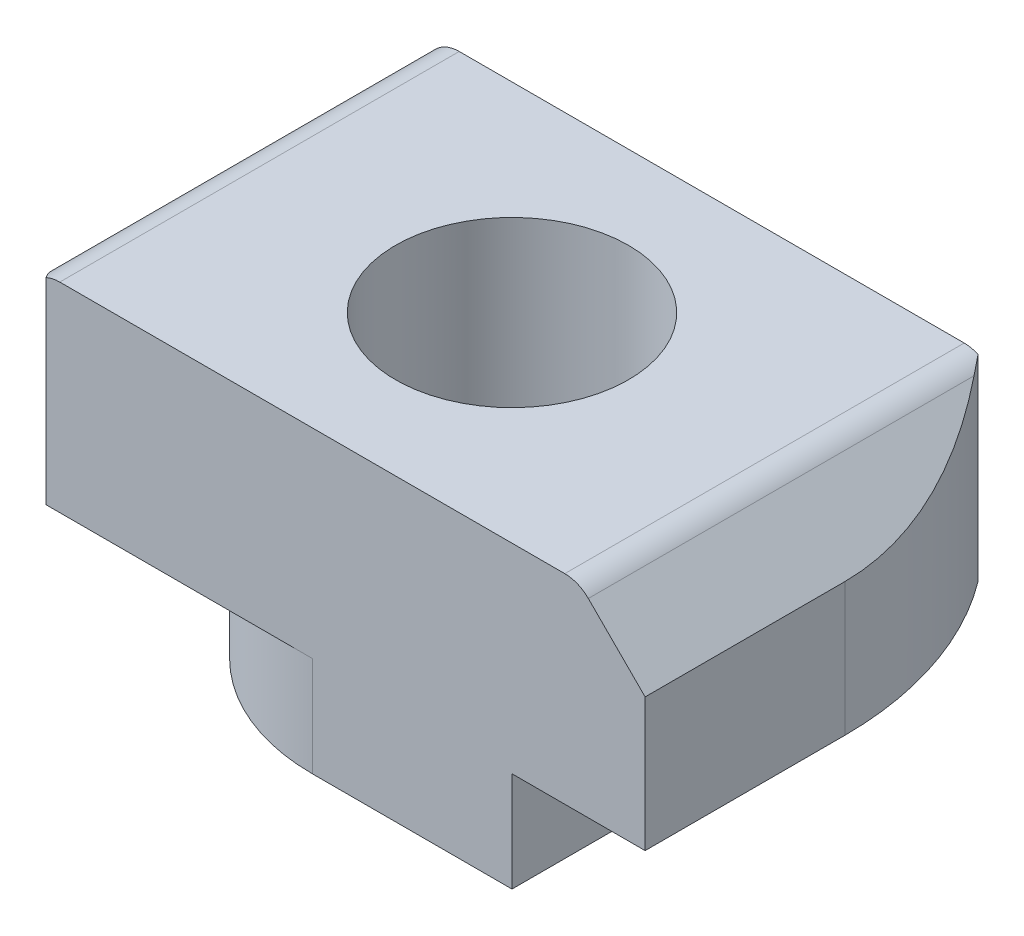
SolidWorks part; units mm, degrees
ref_plane "Спереди" through (0, 0, 0) normal (0, 0, 1) x (1, 0, 0)
ref_plane "Сверху" through (0, 0, 0) normal (0, 1, 0) x (1, 0, 0)
ref_plane "Справа" through (0, 0, 0) normal (1, 0, 0) x (0, 0, -1)
sketch "Эскиз1" plane through (0, 0, 0) normal (0, 0, 1) x (1, 0, 0)
  line L0 (4, 3) -> (5, 2)
  line L1 (0, 0) -> (5, 0)
  line L2 (0, 0) -> (0, 3)
  line L3 (0, 3) -> (4, 3)
  line L4 (5, 0) -> (5, 2)
  line L5 (5, 3) -> (4, 3) construction
  line L6 (5, 2) -> (5, 3) construction
  dimension "D1" = 3
  dimension "D2" = 5
  dimension "D3" = 1
  dimension "D4" = 1
extrude "Бобышка-Вытянуть1" add sketch "Эскиз1" along normal blind 3 and the other way blind 3
mirror "Зеркальное отражение1" about plane through (0, 0, 0) normal (1, 0, 0) of "Бобышка-Вытянуть1"
sketch "Эскиз2" plane through (0, 0, 0) normal (0, -1, 0) x (1, 0, 0)
  line L0 (0, -3) -> (-3, -3)
  line L1 (-5, -3) -> (5, -3) construction
  line L2 (-3, -3) -> (-3, 0)
  line L3 (0, 3) -> (3, 3)
  line L4 (-5, 3) -> (5, 3) construction
  line L5 (3, 3) -> (3, 0)
  circle A0 centre (0, 0) radius 1.75
  arc A1 (0, 3) -> (-3, 0) centre (0, 0) ccw
  arc A2 (0, -3) -> (3, 0) centre (0, 0) ccw
  dimension "D1" = 3.5
extrude "Бобышка-Вытянуть2" add sketch "Эскиз2" along normal blind 1.5
extrude "Вырез-Вытянуть1" cut sketch "Эскиз2<2>" against normal through all contours A0 region at (0, 0, 0)
sketch "Эскиз2<2>" plane through (0, 0, 0) normal (0, -1, 0) x (1, 0, 0) same geometry as "Эскиз2"
sketch "Эскиз3" plane through (0, 0, 0) normal (0, -1, 0) x (1, 0, 0)
  line L0 (0, 0) -> (-8.0092, 0)
  line L1 (8.0092, 5.7229) -> (-8.0092, 5.7229)
  line L2 (8.0092, 5.7229) -> (8.0092, -5.7229)
  line L3 (8.0092, -5.7229) -> (-8.0092, -5.7229)
  line L4 (-8.0092, 5.7229) -> (-8.0092, -5.7229)
  line L5 (8.0092, 5.7229) -> (-8.0092, -5.7229) construction
  line L6 (8.0092, -5.7229) -> (-8.0092, 5.7229) construction
  line L7 (0, 0) -> (0, 5.7229)
  line L8 (0, 0) -> (8.0092, 0)
  line L9 (0, 0) -> (0, -5.7229)
  circle A0 centre (0, 0) radius 5
  line M3 (0, 3) -> (-5, 3)
  line M4 (-5, 3) -> (-5, -3)
extrude "Вырез-Вытянуть2" cut sketch "Эскиз3" against normal through all contours A0 L9 L3 L2 L8 | A0 L7 L1 L4 L0 M4 M3 | A0 M3 M4 region at (-4.706, 0, 2.2658) region at (-5.4422, 0, 3.4591) region at (5.4153, 0, -3.4156)
fillet "Скругление1" radius 0.5 2 edges at (4, 3, 0) (-4, 3, 0)
